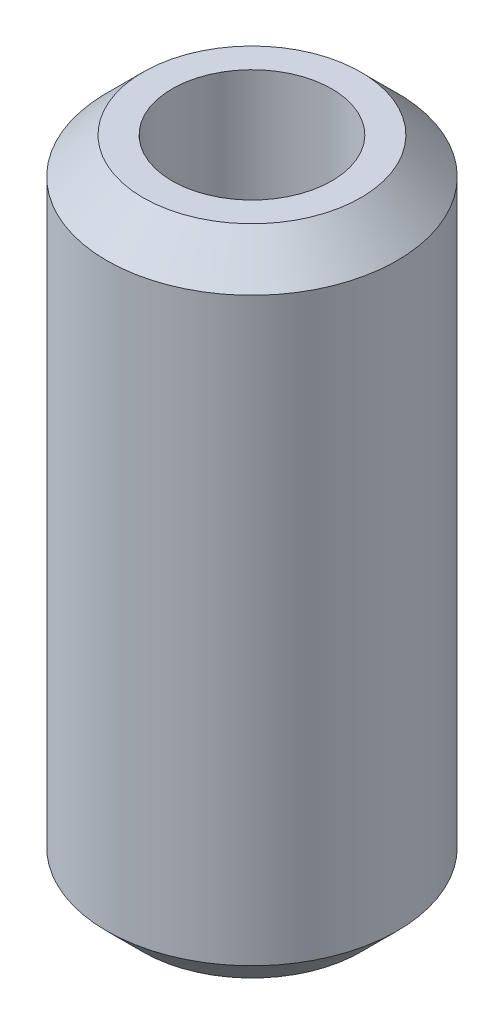
SolidWorks part; units mm, degrees
ref_plane "Спереди" through (0, 0, 0) normal (0, 0, 1) x (1, 0, 0)
ref_plane "Сверху" through (0, 0, 0) normal (0, 1, 0) x (1, 0, 0)
ref_plane "Справа" through (0, 0, 0) normal (1, 0, 0) x (0, 0, -1)
sketch "Эскиз1" plane through (0, 0, 0) normal (0, 1, 0) x (1, 0, 0)
  circle A0 centre (0, 0) radius 2.2
  circle A1 centre (0, 0) radius 4
  dimension "D1" = 4.4
  dimension "D2" = 8
extrude "Бобышка-Вытянуть1" add sketch "Эскиз1" along normal blind 18
chamfer "Фаска1" distance 1 angle 45 2 edges at (0, 0, 4) (0, 18, 4)
